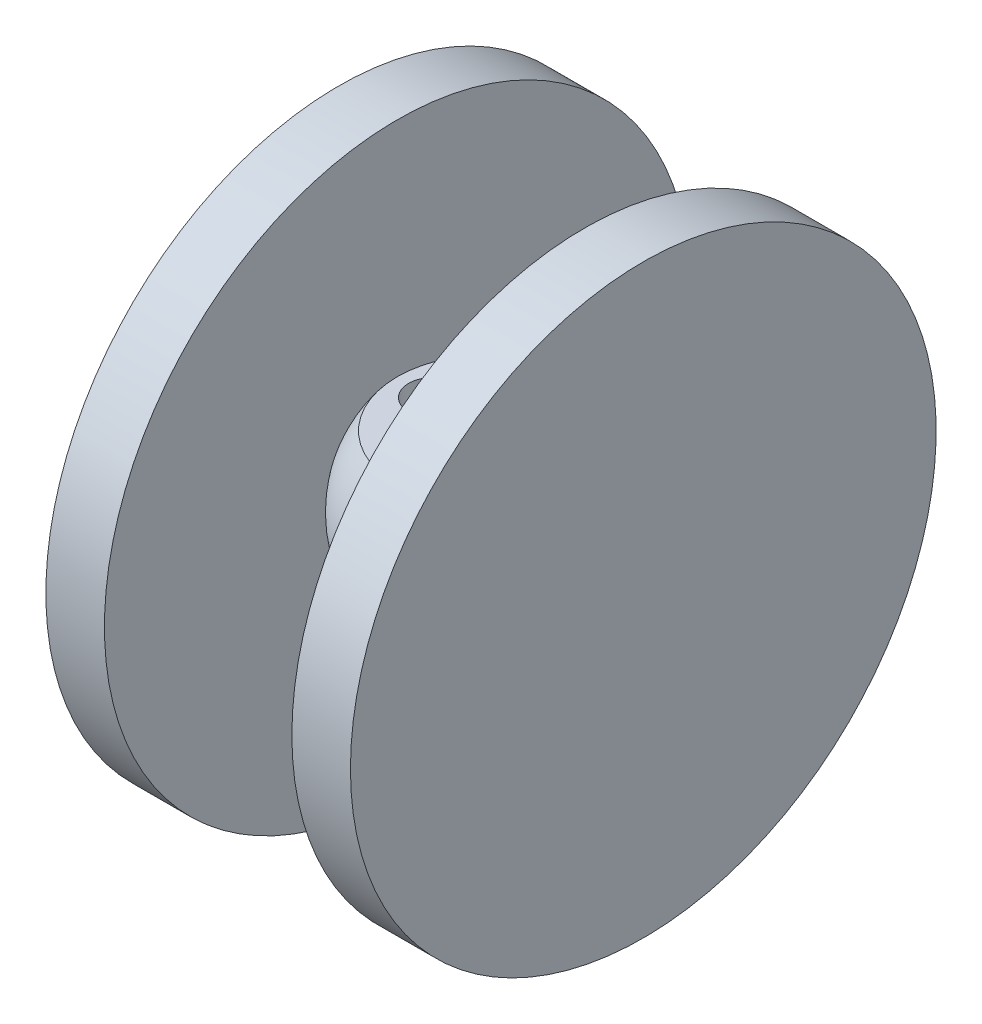
SolidWorks part; units mm, degrees
ref_plane "Front Plane" through (0, 0, 0) normal (0, 0, 1) x (1, 0, 0)
ref_plane "Top Plane" through (0, 0, 0) normal (0, 1, 0) x (1, 0, 0)
ref_plane "Right Plane" through (0, 0, 0) normal (1, 0, 0) x (0, 0, -1)
sketch "Sketch1" plane through (0, 0, 0) normal (1, 0, 0) x (0, 0, -1)
  line L3 (0, 12) -> (16, 12)
  line L4 (0, -20) -> (0, 12)
  arc A0 (0, -20) -> (16, 12) centre (0, 0) ccw
  dimension "D1" = 20
  dimension "D2" = 12
revolve "Revolve2" add sketch "Sketch1" angle 360 about L4
ref_axis "Axis1" through (0, 0, -16.5) along (0, 0, 1)
ref_plane "Plane1" through (0, 0, 0) normal (0.1392, 0.9903, 0) x (0, 0, 1)
ref_plane "Plane2" through (0, 0, 0) normal (-0.1392, 0.9903, 0) x (0, 0, 1)
sketch "Sketch2" plane through (0, 0, 0) normal (0.1392, 0.9903, 0) x (0, 0, 1)
  circle A0 centre (0, 8) radius 4.25
  dimension "D1" = 8.5
  dimension "D2" = 8
extrude "Cut-Extrude1" cut sketch "Sketch2" against normal blind 10 and the other way through all
sketch "Sketch3" plane through (0, 0, 0) normal (-0.1392, 0.9903, 0) x (0, 0, 1)
  circle A0 centre (0, -8) radius 4.25
  dimension "D2" = 8.5
  dimension "D1" = 8
extrude "Cut-Extrude2" cut sketch "Sketch3" against normal blind 10 and the other way through all
chamfer "Chamfer1" distance 10 angle 1 2 edges at (2.3218, -10.4246, 0) (-10.7391, -11.6076, 0) first distance on face at (5.4733, 12, 0) first distance on face at (-5.4733, 12, 0)
sketch "Sketch4" plane through (0, 12, 0) normal (0, 1, 0) x (1, 0, 0)
  line L1 (16, -20) -> (-16, -20)
  line L2 (16, -20) -> (16, 20)
  line L3 (16, 20) -> (-16, 20)
  line L4 (-16, -20) -> (-16, 20)
  line L5 (16, -20) -> (-16, 20) construction
  line L6 (16, 20) -> (-16, -20) construction
  circle A3 centre (0, 0) radius 20 construction
  circle A4 centre (0, 0) radius 16 construction
  point P0 (0, 0)
extrude "Cut-Extrude3" cut sketch "Sketch4" against normal through all flip side to cut
sketch "Sketch5" plane through (-16, 0, -32) normal (1, 0, 0) x (0, 0, -1)
  circle A0 centre (-32, 0) radius 50
  dimension "D1" = 100
extrude "Boss-Extrude1" add sketch "Sketch5" against normal blind 10
sketch "Sketch6" plane through (16, 0, 32) normal (-1, 0, 0) x (0, 0, 1)
  circle A0 centre (-32, 0) radius 50
  circle A1 centre (-32, 0) radius 50 construction
extrude "Boss-Extrude2" add sketch "Sketch6" against normal blind 10
